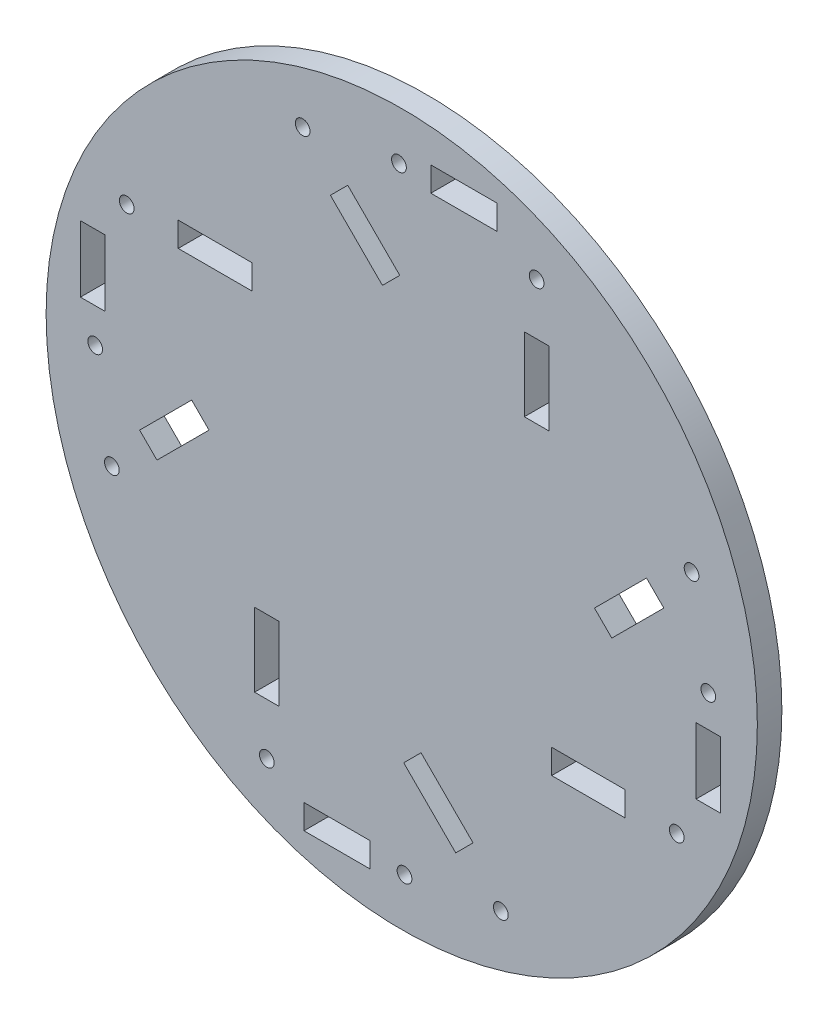
SolidWorks part; units mm, degrees
ref_plane "Front Plane" through (0, 0, 0) normal (0, 0, 1) x (1, 0, 0)
ref_plane "Top Plane" through (0, 0, 0) normal (0, 1, 0) x (1, 0, 0)
ref_plane "Right Plane" through (0, 0, 0) normal (1, 0, 0) x (0, 0, -1)
sketch "Sketch1" plane through (0, 0, 0) normal (0, 0, 1) x (1, 0, 0)
  line L0 (39.2907, 3.9354) -> (49.8973, 14.542)
  line L1 (25, 30.5655) -> (30, 30.5655)
  line L2 (25, 30.5655) -> (25, 45.5655)
  line L3 (25, 45.5655) -> (30, 45.5655)
  line L4 (30, 30.5655) -> (30, 45.5655)
  line L5 (39.2907, 3.9354) -> (42.8263, 0.3999)
  line L6 (42.8263, 0.3999) -> (53.4329, 11.0065)
  line L7 (49.8973, 14.542) -> (53.4329, 11.0065)
  line L8 (30.5655, -25) -> (45.5655, -25)
  line L9 (30.5655, -25) -> (30.5655, -30)
  line L10 (30.5655, -30) -> (45.5655, -30)
  line L11 (45.5655, -25) -> (45.5655, -30)
  line L12 (3.9354, -39.2907) -> (14.542, -49.8973)
  line L13 (3.9354, -39.2907) -> (0.3999, -42.8263)
  line L14 (0.3999, -42.8263) -> (11.0065, -53.4329)
  line L15 (14.542, -49.8973) -> (11.0065, -53.4329)
  line L16 (-25, -30.5655) -> (-25, -45.5655)
  line L17 (-25, -30.5655) -> (-30, -30.5655)
  line L18 (-30, -30.5655) -> (-30, -45.5655)
  line L19 (-25, -45.5655) -> (-30, -45.5655)
  line L20 (-39.2907, -3.9354) -> (-49.8973, -14.542)
  line L21 (-39.2907, -3.9354) -> (-42.8263, -0.3999)
  line L22 (-42.8263, -0.3999) -> (-53.4329, -11.0065)
  line L23 (-49.8973, -14.542) -> (-53.4329, -11.0065)
  line L24 (-30.5655, 25) -> (-45.5655, 25)
  line L25 (-30.5655, 25) -> (-30.5655, 30)
  line L26 (-30.5655, 30) -> (-45.5655, 30)
  line L27 (-45.5655, 25) -> (-45.5655, 30)
  line L28 (-3.9354, 39.2907) -> (-14.542, 49.8973)
  line L29 (-3.9354, 39.2907) -> (-0.3999, 42.8263)
  line L30 (-0.3999, 42.8263) -> (-11.0065, 53.4329)
  line L31 (-14.542, 49.8973) -> (-11.0065, 53.4329)
  line L32 (27.5, 56.0655) -> (27.5, 45.5655) construction
  line L33 (-19.9345, -65) -> (-19.9345, -60)
  line L34 (65, -19.4345) -> (60, -19.4345)
  line L35 (65, -19.4345) -> (65, -5.9345)
  line L36 (65, -5.9345) -> (60, -5.9345)
  line L37 (60, -19.4345) -> (60, -5.9345)
  line L38 (-19.9345, -65) -> (-6.4345, -65)
  line L39 (-19.9345, -60) -> (-6.4345, -60)
  line L40 (-6.4345, -65) -> (-6.4345, -60)
  line L41 (-65.5, 19.9345) -> (-60.5, 19.9345)
  line L42 (-65.5, 19.9345) -> (-65.5, 6.4345)
  line L43 (-60.5, 19.9345) -> (-60.5, 6.4345)
  line L44 (-65.5, 6.4345) -> (-60.5, 6.4345)
  line L45 (19.4345, 65.5) -> (19.4345, 60.5)
  line L46 (19.4345, 65.5) -> (5.9345, 65.5)
  line L47 (19.4345, 60.5) -> (5.9345, 60.5)
  line L48 (5.9345, 65.5) -> (5.9345, 60.5)
  line L49 (62.5, -5.9345) -> (62.5, 0.5655) construction
  circle A0 centre (0, 0) radius 58.6265 construction
  circle A1 centre (0, 0) radius 72.5
  circle A2 centre (27.5, 56.0655) radius 1.5
  circle A3 centre (59.0897, 20.1989) radius 1.5
  circle A4 centre (56.0655, -27.5) radius 1.5
  circle A5 centre (20.1989, -59.0897) radius 1.5
  circle A6 centre (-27.5, -56.0655) radius 1.5
  circle A7 centre (-59.0897, -20.1989) radius 1.5
  circle A8 centre (-56.0655, 27.5) radius 1.5
  circle A9 centre (-20.1989, 59.0897) radius 1.5
  circle A10 centre (62.5, 0.5655) radius 1.5
  circle A11 centre (0.5655, -62.5) radius 1.5
  circle A12 centre (-62.5, -0.5655) radius 1.5
  circle A13 centre (-0.5655, 62.5) radius 1.5
  dimension "D1" = 145
  dimension "D4" = 3
  dimension "D6" = 10.5
  dimension "D13" = 3
  dimension "D3" = 15
  dimension "D7" = 13.5
  dimension "D8" = 5
  dimension "D9" = 50
  dimension "D10" = 30
  dimension "D12" = 6.5
  dimension "D2" = 8
  dimension "D5" = 8
  dimension "D11" = 4
  dimension "D14" = 4
extrude "Boss-Extrude1" add sketch "Sketch1" along normal blind 5 contours L7 A1 L4 L1 L2 L3 L30 L29 L28 L31 L26 L25 L24 L27 L22 L21 L20 L23 L18 L17 L16 L19 L14 L13 L12 L15 L10 L9 L8 L11 L6 L5 L0 region at (0.0043, -0.0043, 0)
